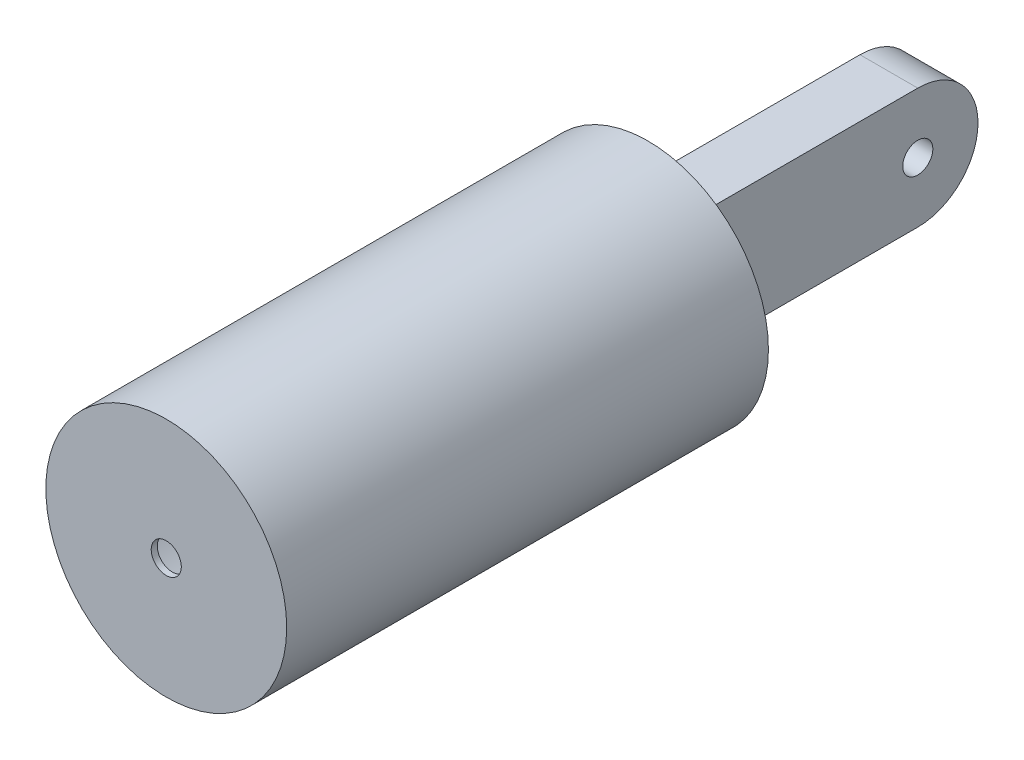
SolidWorks part; units mm, degrees
ref_plane "Front Plane" through (0, 0, 0) normal (0, 0, 1) x (1, 0, 0)
ref_plane "Top Plane" through (0, 0, 0) normal (0, 1, 0) x (1, 0, 0)
ref_plane "Right Plane" through (0, 0, 0) normal (1, 0, 0) x (0, 0, -1)
sketch "Sketch1" plane through (0, 0, 0) normal (0, 0, 1) x (1, 0, 0)
  circle A0 centre (0, 0) radius 10
  dimension "D1" = 20
extrude "Boss-Extrude1" add sketch "Sketch1" along normal mid plane 40
sketch "Sketch3" plane through (0, 0, 0) normal (0, 0, 1) x (1, 0, 0)
  circle A0 centre (0, 0) radius 9.75
  dimension "D1" = 19.5
extrude "Cut-Extrude1" cut sketch "Sketch3" against normal mid plane 39
sketch "Sketch4" plane through (0, 0, 20) normal (0, 0, 1) x (1, 0, 0)
  circle A0 centre (0, 0) radius 1.25
  dimension "D1" = 2.5
extrude "Cut-Extrude2" cut sketch "Sketch4" against normal blind 1
sketch "Sketch5" plane through (0, 0, 0) normal (1, 0, 0) x (0, 0, -1)
  line L0 (20, 5) -> (20, -5)
  line L1 (20, -10) -> (20, 10) construction
  line L2 (20, 5) -> (40, 5)
  line L4 (40, -5) -> (20, -5)
  arc A0 (40, -5) -> (40, 5) centre (40, 0) ccw
  point P4 (20, 0)
  dimension "D2" = 20
  dimension "D3" = 5
  dimension "D1" = 10
extrude "Boss-Extrude2" add sketch "Sketch5" along normal mid plane 4.8
sketch "Sketch6" [suppressed] plane through (2.4, 0, 0) normal (1, 0, 0) x (0, 0, -1)
  circle A0 centre (50, 0) radius 1.25
  arc A1 (50, -5) -> (50, 5) centre (50, 0) ccw construction
  dimension "D1" = 2.5
extrude "Cut-Extrude3" [suppressed] cut sketch "Sketch6" against normal blind 10
sketch "Sketch7" plane through (2.4, 0, 0) normal (1, 0, 0) x (0, 0, -1)
  circle A0 centre (40, 0) radius 1.25
  arc A1 (40, -5) -> (40, 5) centre (40, 0) ccw construction
  dimension "D1" = 2.5
extrude "Cut-Extrude4" cut sketch "Sketch7" against normal blind 10
ref_axis "Axis1" [suppressed] through (-2.4, 0, -50) along (1, 0, 0)
ref_point "Point1" [suppressed]
ref_axis "Axis2" through (-2.4, 0, -40) along (1, 0, 0)
ref_point "Point2"
